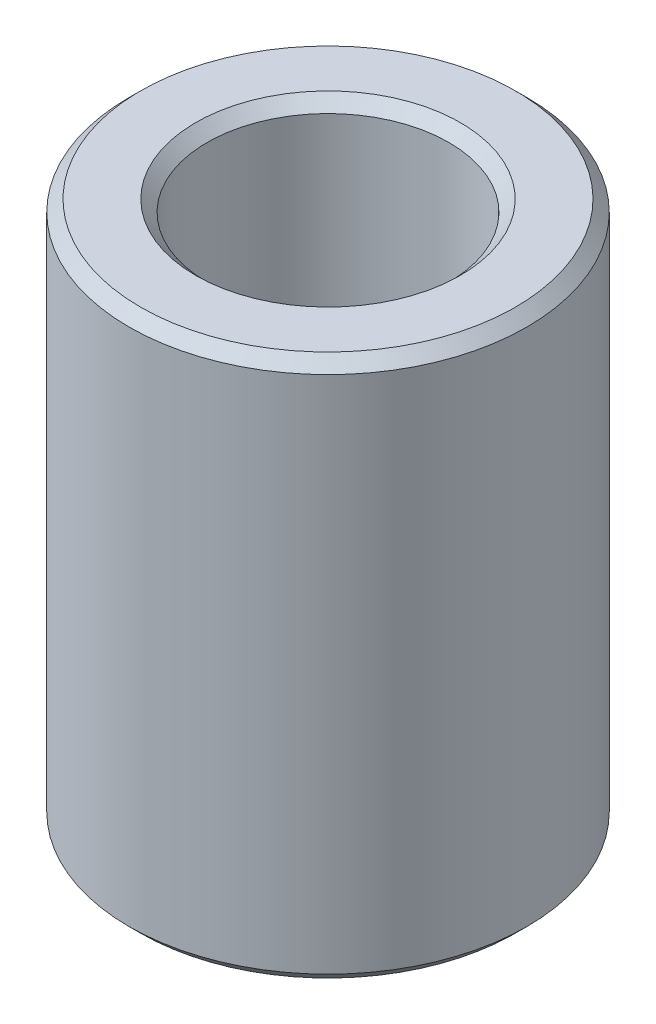
SolidWorks part; units mm, degrees
ref_plane "Front Plane" through (0, 0, 0) normal (0, 0, 1) x (1, 0, 0)
ref_plane "Top Plane" through (0, 0, 0) normal (0, 1, 0) x (1, 0, 0)
ref_plane "Right Plane" through (0, 0, 0) normal (1, 0, 0) x (0, 0, -1)
sketch "Sketch1" plane through (0, 0, 0) normal (0, 1, 0) x (1, 0, 0)
  circle A0 centre (0, 0) radius 52.5
  dimension "SLEEVE_OD" = 105
extrude "Boss-Extrude1" add sketch "Sketch1" along normal blind 143.1267
sketch "Sketch2" plane through (0, 0, 0) normal (0, 1, 0) x (1, 0, 0)
  circle A0 centre (0, 0) radius 31.9163
  dimension "BORE_D" = 63.8326
extrude "Cut-Extrude1" cut sketch "Sketch2" along normal through all
chamfer "Chamfer1" distance 3.0284 angle 45 4 edges at (0, 143.1267, 31.9163) (0, 0, 31.9163) (0, 0, 52.5) (0, 143.1267, 52.5)
